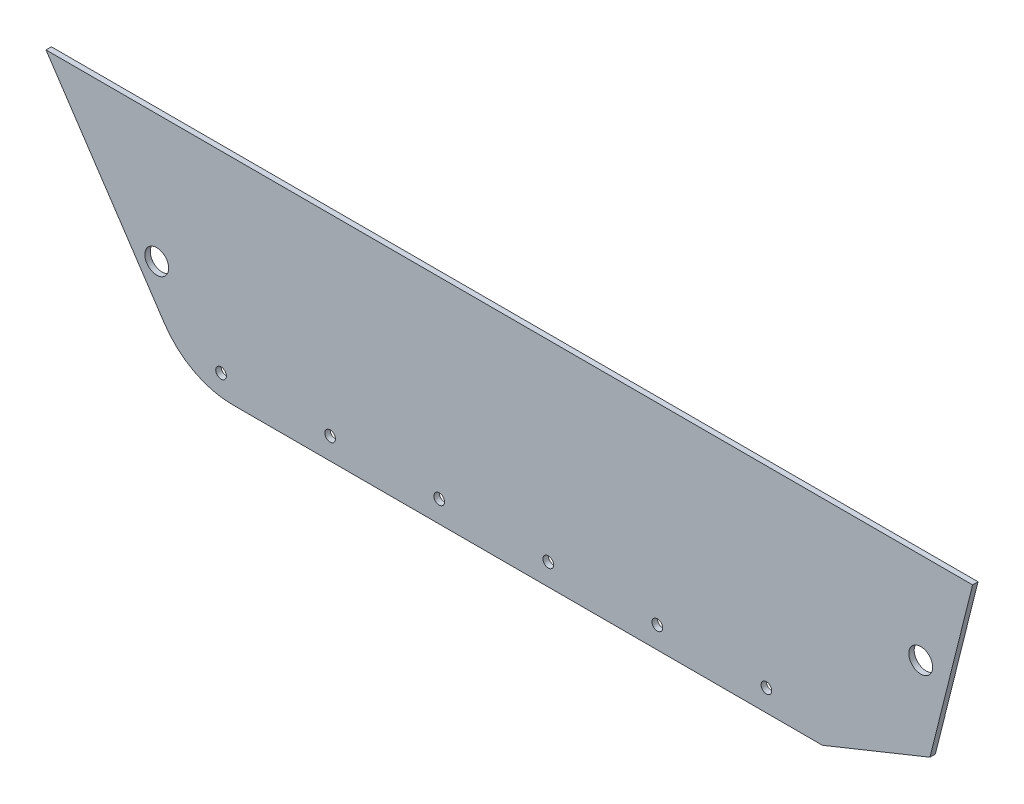
SolidWorks part; units mm, degrees
material "5052-H34"
ref_plane "Front Plane" through (0, 0, 0) normal (0, 0, 1) x (1, 0, 0)
ref_plane "Top Plane" through (0, 0, 0) normal (0, 1, 0) x (1, 0, 0)
ref_plane "Right Plane" through (0, 0, 0) normal (1, 0, 0) x (0, 0, -1)
sketch "Sketch1" plane through (0, 0, 0) normal (0, 0, 1) x (1, 0, 0)
  line L6 (-98.8794, 3.851) -> (-31.8794, -96.649)
  line L7 (428.1206, 28.9396) -> (403.1206, -71.149)
  line L9 (403.1206, -71.149) -> (366, -96.649)
  line L10 (-31.8794, -96.649) -> (366, -96.649)
  line L12 (-98.8794, 3.851) -> (-115.6052, 28.9396)
  line L13 (-115.6052, 28.9396) -> (428.1206, 28.9396)
  circle A0 centre (-12.8794, -83.899) radius 3.125
  circle A1 centre (51.1206, -83.899) radius 3.125
  circle A2 centre (115.1206, -83.899) radius 3.125
  circle A3 centre (179.1206, -83.899) radius 3.125
  circle A4 centre (243.1206, -83.899) radius 3.125
  circle A5 centre (307.1206, -83.899) radius 3.125
  point P0 (-48.8794, -71.149)
  point P2 (-31.8794, -96.649)
  point P8 (48, -83.899)
  point P9 (403.1206, -71.149)
  dimension "D2" = 64
  dimension "D4" = 64
  dimension "D15" = 6.25
  dimension "D1" = 25.5
  dimension "D3" = 75
  dimension "D5" = 25
  dimension "D6" = 96
  dimension "D7" = 527
  dimension "D8" = 180
  dimension "D9" = 64
  dimension "D10" = 64
  dimension "D11" = 64
  dimension "D12" = 123.69
  dimension "D13" = 12.75
  dimension "D14" = 543.7258
  dimension "D16" = 366
extrude "Boss-Extrude1" add sketch "Sketch1" along normal blind 3.175 contours L12 L13 L7 L9 L10 L6
extrude "Cut-Extrude1" cut sketch "Sketch1<4>" along normal through all contours A0 | A1 | A2 | A3 | A4 | A5 region at (-12.8794, -83.899, 0)
sketch "Sketch1<4>" plane through (0, 0, 0) normal (0, 0, 1) x (1, 0, 0) same geometry as "Sketch1"
sketch "Sketch2" plane through (0, 0, 0) normal (0, 0, -1) x (-1, 0, 0)
  circle A0 centre (-275.1206, -83.899) radius 6.5
  circle A2 centre (-233.5603, -132.5687) radius 6.5
  circle A3 centre (-192, -83.899) radius 6.5
  circle A4 centre (-128, -83.899) radius 6.5
  circle A5 centre (-64, -83.899) radius 6.5
  circle A6 centre (0, -83.899) radius 6.5
  dimension "D2" = 0
  dimension "D3" = 64
  dimension "D4" = 64
  dimension "D5" = 64
  dimension "D6" = 64
  dimension "D7" = 64
  dimension "D1" = 32
sketch "Sketch5" plane through (0, 0, 0) normal (0, 0, -1) x (-1, 0, 0)
  line L0 (48.8794, -71.149) -> (-14.2353, -96.649)
  line L1 (31.8794, -96.649) -> (-366, -96.649) construction
  line L2 (-14.2353, -96.649) -> (31.8794, -96.649)
  line L3 (31.8794, -96.649) -> (48.8794, -71.149)
  line L6 (-366, -96.649) -> (-403.1206, -71.149)
  line L7 (-403.1206, -71.149) -> (-352, -71.149)
  line L9 (-352, -71.149) -> (-326.5, -96.649)
  line L11 (-366, -96.649) -> (-326.5, -96.649)
  dimension "D1" = 22
  dimension "D2" = 45
extrude "Cut-Extrude2" [suppressed] cut sketch "Sketch5" against normal up to next
sketch "Sketch6" plane through (0, 0, 3.175) normal (0, 0, 1) x (1, 0, 0)
  line L0 (-48.8794, -71.149) -> (14.2353, -96.649)
  line L1 (-31.8794, -96.649) -> (366, -96.649) construction
  line L2 (14.2353, -96.649) -> (-31.8794, -96.649)
  line L3 (-31.8794, -96.649) -> (-48.8794, -71.149)
  dimension "D1" = 158
fillet "Fillet1" radius 48 1 edges at (-31.8794, -96.649, 1.5875)
sketch "Sketch7" plane through (0, 0, 3.175) normal (0, 0, 1) x (1, 0, 0)
  line L0 (403.1206, -71.149) -> (340.0059, -96.649)
  line L1 (-31.8794, -96.649) -> (366, -96.649) construction
  line L2 (340.0059, -96.649) -> (366, -96.649)
  line L3 (366, -96.649) -> (403.1206, -71.149)
  dimension "D1" = 22
extrude "Cut-Extrude3" cut sketch "Sketch7" against normal blind 10
sketch "Sketch9" plane through (0, 0, 0) normal (0, 0, -1) x (-1, 0, 0)
  line L0 (-403.1206, -71.149) -> (48.8794, -71.149)
  line L1 (48.8794, -71.149) -> (48.8794, -114.9143)
  line L2 (48.8794, -114.9143) -> (-403.1206, -114.9143)
  line L3 (-403.1206, -114.9143) -> (-403.1206, -71.149)
extrude "Cut-Extrude4" [suppressed] cut sketch "Sketch9" against normal blind 10
sketch "Sketch12" plane through (0, 0, 3.175) normal (0, 0, 1) x (1, 0, 0)
  circle A0 centre (397.6778, -24.6104) radius 7
  dimension "D1" = 14
extrude "Cut-Extrude5" cut sketch "Sketch12" against normal up to next
sketch "Sketch13" plane through (0, 0, 3.175) normal (0, 0, 1) x (1, 0, 0)
  line L2 (397.6778, -24.6104) -> (397.6778, -124.8724) construction
  line L3 (-115.6052, 28.9396) -> (428.1206, 28.9396) construction
  circle A0 centre (-50.6052, -46.0604) radius 7
  dimension "D2" = 14
  dimension "D1" = 65
  dimension "D3" = 75
extrude "Cut-Extrude6" cut sketch "Sketch13" against normal blind 10
